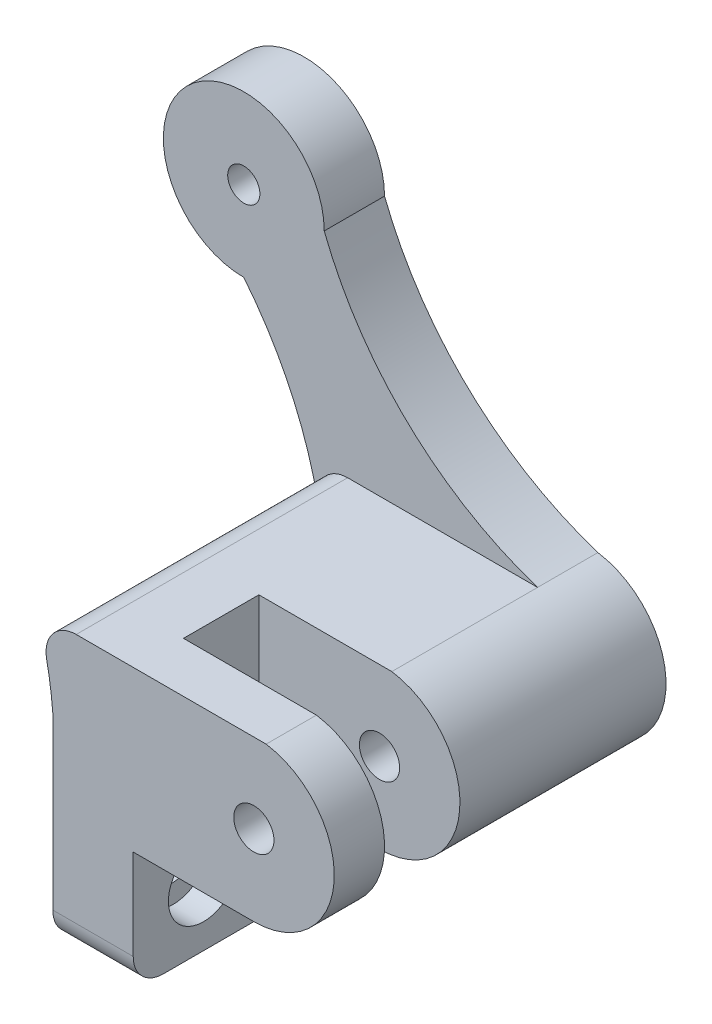
SolidWorks part; units mm, degrees
ref_plane "Ön Düzlem" through (0, 0, 0) normal (0, 0, 1) x (1, 0, 0)
ref_plane "Üst Düzlem" through (0, 0, 0) normal (0, 1, 0) x (1, 0, 0)
ref_plane "Sağ Düzlem" through (0, 0, 0) normal (1, 0, 0) x (0, 0, -1)
sketch "Sketch1" plane through (0, 0, 0) normal (0, 0, 1) x (1, 0, 0)
  line L0 (0, -8) -> (-12, -8)
  line L1 (-12, -8) -> (-12, -20)
  line L2 (-12, -20) -> (-20, -20)
  line L3 (-20, 0) -> (-20, -20)
  line L5 (-21.5344, 7.9057) -> (1.2247, 7.9057)
  arc A0 (0, -8) -> (1.2247, 7.9057) centre (0, 0) ccw
  arc A1 (-20, 28) -> (-28, 20) centre (-28, 28) ccw
  circle A2 centre (0, 0) radius 2
  circle A3 centre (-28, 28) radius 1.6
  arc A4 (-20, 28) -> (1.2247, 7.9057) centre (11.8724, 40.4089) ccw
  arc A5 (-28, 20) -> (-20, 0) centre (-56.4146, -2.9658) cw
  dimension "D1" = 3.2
  dimension "D2" = 16
  dimension "D3" = 16
  dimension "D4" = 4
  dimension "D5" = 28
  dimension "D6" = 28
  dimension "D7" = 12
  dimension "D8" = 8
  dimension "D9" = 20
  dimension "D10" = 12
extrude "Boss-Extrude6" add sketch "Sketch1" along normal blind 6 contours L5 A5 L3 L2 L1 L0 A0 A2 | A1 A5 L5 A4 A3 region at (-8.8297, -2.6287, 0) region at (-22.0088, 20.9264, 0)
extrude "Boss-Extrude7" add sketch "Sketch1<6>" along normal blind 33 contours L5 A5 L3 L2 L1 L0 A0 A2 region at (-8.8297, -2.6287, 0)
sketch "Sketch1<6>" plane through (0, 0, 0) normal (0, 0, 1) x (1, 0, 0) same geometry as "Sketch1"
sketch "Sketch2" plane through (0, 0, 33) normal (0, 0, 1) x (1, 0, 0)
  line L0 (-12, -8) -> (-12, 7.9057)
  line L5 (1.2247, 7.9057) -> (-21.5344, 7.9057)
  line L6 (-20, 0) -> (-20, -20)
  line L7 (-20, -20) -> (-12, -20)
  line L8 (-12, -20) -> (-12, -8)
  line L9 (-12, -8) -> (0, -8)
  line L10 (1.2247, 7.9057) -> (-12, 7.9057)
  line L14 (-12, -8) -> (0, -8)
  arc A2 (-20, 0) -> (-21.5344, 7.9057) centre (-56.4146, -2.9658) ccw
  arc A3 (0, -8) -> (1.2247, 7.9057) centre (0, 0) ccw
  arc A5 (0, -8) -> (1.2247, 7.9057) centre (0, 0) ccw
  dimension "D1" = 0
extrude "Cut-Extrude1" cut sketch "Sketch2" against normal blind 7.5 from offset 5 offset against normal yes
fillet "Fillet1" radius 3 2 edges at (-16, -20, 33) (-16, -20, 0)
sketch "Sketch3" plane through (-12, 0, 0) normal (1, 0, 0) x (0, 0, -1)
  line L0 (-30, -20) -> (-3, -20) construction
  line L1 (-33, -8) -> (-33, -17) construction
  line L2 (0, -8) -> (0, -17) construction
  circle A0 centre (-26, -14) radius 1.6
  circle A1 centre (-7, -14) radius 1.6
  dimension "D1" = 3.2
  dimension "D2" = 3.2
  dimension "D3" = 6
  dimension "D4" = 6
  dimension "D5" = 7
  dimension "D6" = 7
extrude "Cut-Extrude2" cut sketch "Sketch3" against normal blind 17.5
sketch "Sketch4" plane through (-12, 0, 0) normal (1, 0, 0) x (0, 0, -1)
  circle A0 centre (-26, -14) radius 1.6 construction
  circle A1 centre (-26, -14) radius 1.6
  circle A3 centre (-26, -14) radius 3.5
  circle A4 centre (-7, -14) radius 3.5
  dimension "D1" = 7
  dimension "D2" = 7
extrude "Cut-Extrude3" cut sketch "Sketch4" against normal blind 3
fillet "Fillet2" radius 3 1 edges at (-21.5344, 7.9057, 19.5)
sketch "Sketch5" plane through (0, 0, 0) normal (0, 0, -1) x (-1, 0, 0)
  circle A1 centre (0, 0) radius 3.5
extrude "Cut-Extrude6" cut sketch "Sketch5" against normal blind 4
